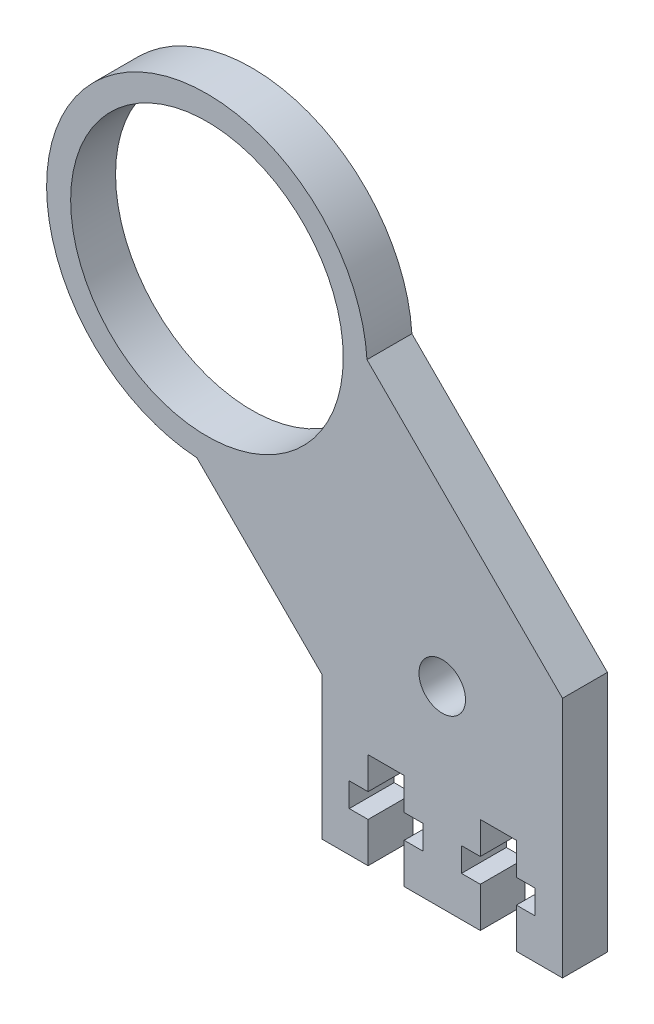
SolidWorks part; units mm, degrees
ref_plane "Front Plane" through (0, 0, 0) normal (0, 0, 1) x (1, 0, 0)
ref_plane "Top Plane" through (0, 0, 0) normal (0, 1, 0) x (1, 0, 0)
ref_plane "Right Plane" through (0, 0, 0) normal (1, 0, 0) x (0, 0, -1)
sketch "Sketch1" plane through (0, 0, 0) normal (0, 0, 1) x (1, 0, 0)
  line L0 (0, 0) -> (-29.3449, 29.3449) construction
  line L1 (0, 0) -> (0, 31.0325) construction
  line L2 (-15, -6.2132) -> (-15, -24)
  line L3 (-15, -24) -> (15, -24)
  line L4 (15, -24) -> (15, 6.2132)
  line L5 (0, 0) -> (0, -24) construction
  line L6 (15, 6.2132) -> (-9.3842, 30.5974)
  line L7 (-15, -6.2132) -> (-30.5974, 9.3842)
  line L8 (10.6066, 10.6066) -> (-18.7383, 39.9515) construction
  line L9 (-10.6066, -10.6066) -> (-39.9515, 18.7383) construction
  circle A0 centre (0, 0) radius 2.9
  arc A1 (-9.3842, 30.5974) -> (-30.5974, 9.3842) centre (-29.3449, 29.3449) ccw
  dimension "D1" = 5.8
  dimension "D3" = 40
  dimension "D2" = 41.5
  dimension "D4" = 45
  dimension "D5" = 24
  dimension "D6" = 30
  dimension "D7" = 15
  dimension "D8" = 15
extrude "Boss-Extrude1" add sketch "Sketch1" along normal blind 5.6
sketch "Sketch2" plane through (0, 0, 5.6) normal (0, 0, 1) x (1, 0, 0)
  circle A0 centre (-29.3449, 29.3449) radius 17
  dimension "D1" = 34
extrude "Cut-Extrude1" cut sketch "Sketch2" against normal through all
sketch "Sketch3" plane through (0, 0, 5.6) normal (0, 0, 1) x (1, 0, 0)
  line L0 (-15, -24) -> (15, -24) construction
  line L1 (-9.25, -24) -> (-4.75, -24)
  line L2 (-9.25, -24) -> (-9.25, -19)
  line L3 (-9.25, -12) -> (-4.75, -12)
  line L4 (-4.75, -24) -> (-4.75, -19)
  line L5 (0, 0) -> (0, -24) construction
  line L6 (-4.75, -16) -> (-2.4, -16)
  line L7 (-11.6, -16) -> (-9.25, -16)
  line L8 (-11.6, -16) -> (-11.6, -19)
  line L9 (-11.6, -19) -> (-9.25, -19)
  line L10 (-2.4, -16) -> (-2.4, -19)
  line L11 (-9.25, -16) -> (-9.25, -12)
  line L12 (-4.75, -19) -> (-2.4, -19)
  line L13 (-4.75, -16) -> (-4.75, -12)
  line L14 (4.75, -16) -> (4.75, -12)
  line L15 (4.75, -19) -> (2.4, -19)
  line L16 (9.25, -16) -> (9.25, -12)
  line L17 (2.4, -16) -> (2.4, -19)
  line L18 (11.6, -19) -> (9.25, -19)
  line L19 (11.6, -16) -> (11.6, -19)
  line L20 (11.6, -16) -> (9.25, -16)
  line L21 (4.75, -16) -> (2.4, -16)
  line L22 (4.75, -24) -> (4.75, -19)
  line L23 (9.25, -12) -> (4.75, -12)
  line L24 (9.25, -24) -> (9.25, -19)
  line L25 (9.25, -24) -> (4.75, -24)
  point P6 (-7, -12)
  point P18 (-10.425, -19)
  dimension "D1" = 4.5
  dimension "D2" = 7
  dimension "D3" = 12
  dimension "D4" = 9.2
  dimension "D5" = 3
  dimension "D6" = 5
extrude "Cut-Extrude2" cut sketch "Sketch3" against normal through all
equation "\"smallPulleyTeeth\"= 15"
equation "\"largePulleyTeeth\"= 30"
equation "\"eighthThick\"= 2.9mm"
equation "\"sixteenthThick\" = 1.7mm"
equation "\"quarterThick\"=5.6mm"
equation "\"OD\" = 150mm"
equation "\"puckAngle\" = 60.5deg"
equation "\"puckDiam\" = 76.5mm"
equation "\"axlePress\" = 5.8mm"
equation "\"D1@Sketch1\"=\"axlePress\""
equation "\"D1@Boss-Extrude1\"=\"quarterThick\""
equation "\"press\" = 0.2mm"
equation "\"wheelClear\" = 0.3mm"
equation "\"10-32clear\" = 4.5mm"
equation "\"D1@Sketch3\"=\"10-32clear\""
equation "\"6-32clear\" = 3.3mm"
equation "\"8-32clear\" = 4.0mm"
equation "\"wheelHeight\" = 24mm"
equation "\"D5@Sketch1\"=\"wheelHeight\""
